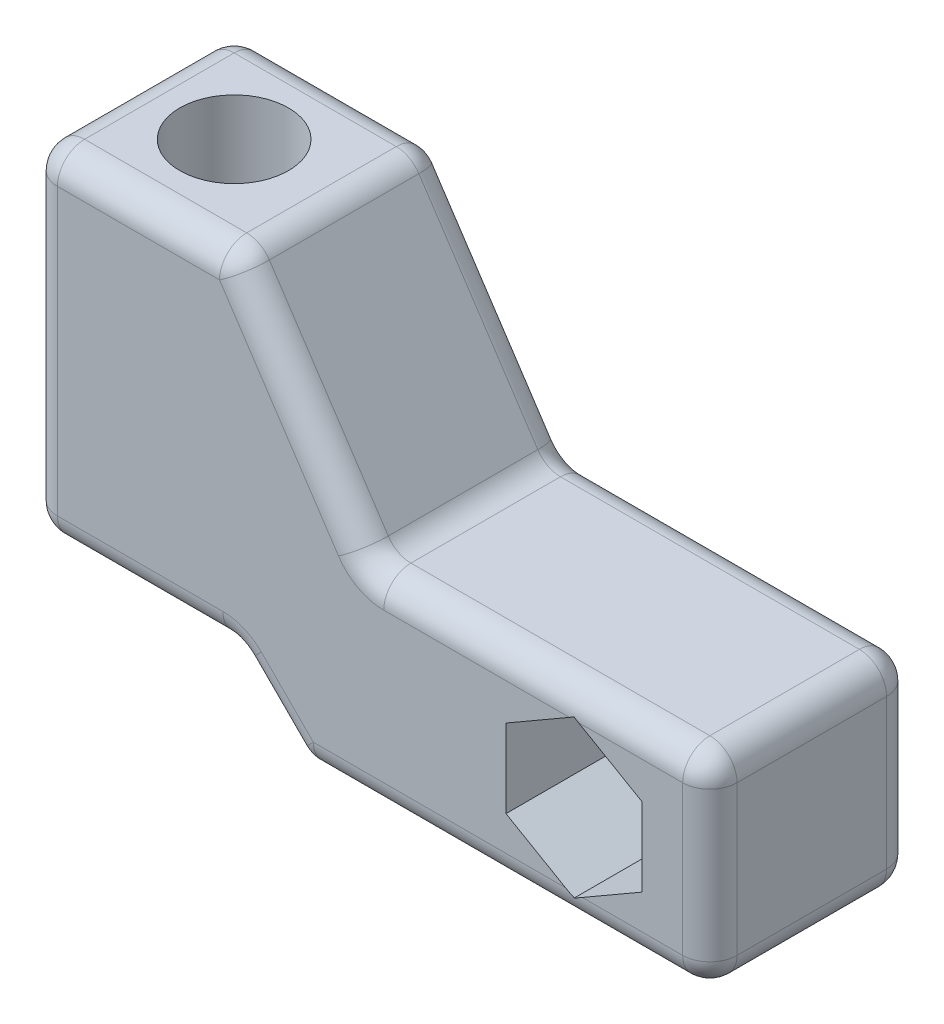
SolidWorks part; units mm, degrees
ref_plane "Front Plane" through (0, 0, 0) normal (0, 0, 1) x (1, 0, 0)
ref_plane "Top Plane" through (0, 0, 0) normal (0, 1, 0) x (1, 0, 0)
ref_plane "Right Plane" through (0, 0, 0) normal (1, 0, 0) x (0, 0, -1)
sketch "Sketch1" plane through (0, 0, 0) normal (0, 0, 1) x (1, 0, 0)
  line L0 (0, 0) -> (15, 0)
  line L1 (20, -5) -> (50, -5)
  line L2 (0, 0) -> (0, 25)
  line L3 (0, 25) -> (15, 25)
  line L4 (50, -5) -> (50, 10)
  line L5 (15, 0) -> (20, -5)
  line L6 (50, 10) -> (24.9335, 10)
  line L7 (24.9335, 10) -> (15, 25)
  dimension "D1" = 25
  dimension "D2" = 15
  dimension "D3" = 15
  dimension "D4" = 15
  dimension "D5" = 5
  dimension "D6" = 50
  dimension "D7" = 135
extrude "Boss-Extrude1" add sketch "Sketch1" along normal blind 15
sketch "Sketch2" plane through (0, 25, 0) normal (0, 1, 0) x (1, 0, 0)
  line L0 (0, -15) -> (0, 0) construction
  line L1 (15, -15) -> (0, -15) construction
  circle A0 centre (7.5, -7.5) radius 4
  point P4 (0, -7.5)
  point P7 (7.5, -15)
  dimension "D1" = 8
extrude "Cut-Extrude1" cut sketch "Sketch2" against normal through all
sketch "Sketch3" plane through (0, 0, 15) normal (0, 0, 1) x (1, 0, 0)
  line L0 (50, -5) -> (50, 10) construction
  line L1 (45, -0.4676) -> (45, 5.3059)
  line L2 (45, 5.3059) -> (40, 8.1927)
  line L3 (40, 8.1927) -> (35, 5.3059)
  line L4 (35, 5.3059) -> (35, -0.4676)
  line L5 (35, -0.4676) -> (40, -3.3543)
  line L6 (40, -3.3543) -> (45, -0.4676)
  circle A0 centre (40, 2.4192) radius 5 construction
  dimension "D1" = 10
  dimension "D2" = 10
extrude "Cut-Extrude2" cut sketch "Sketch3" against normal blind 15
fillet "Fillet1" radius 2 24 edges at (37.4667, 10, 15) (37.4667, 10, 0) (50, -5, 7.5) (50, 2.5, 15) (50, 10, 7.5) (50, 2.5, 0) (24.9335, 10, 7.5) (19.9667, 17.5, 15) (15, 25, 7.5) (19.9667, 17.5, 0) (20, -5, 7.5) (15, 0, 7.5) (0, 0, 7.5) (0, 12.5, 0) (7.5, 0, 0) (17.5, -2.5, 0) (35, -5, 0) (0, 12.5, 15) (7.5, 0, 15) (17.5, -2.5, 15) (35, -5, 15) (7.5, 25, 0) (7.5, 25, 15) (0, 25, 7.5)
